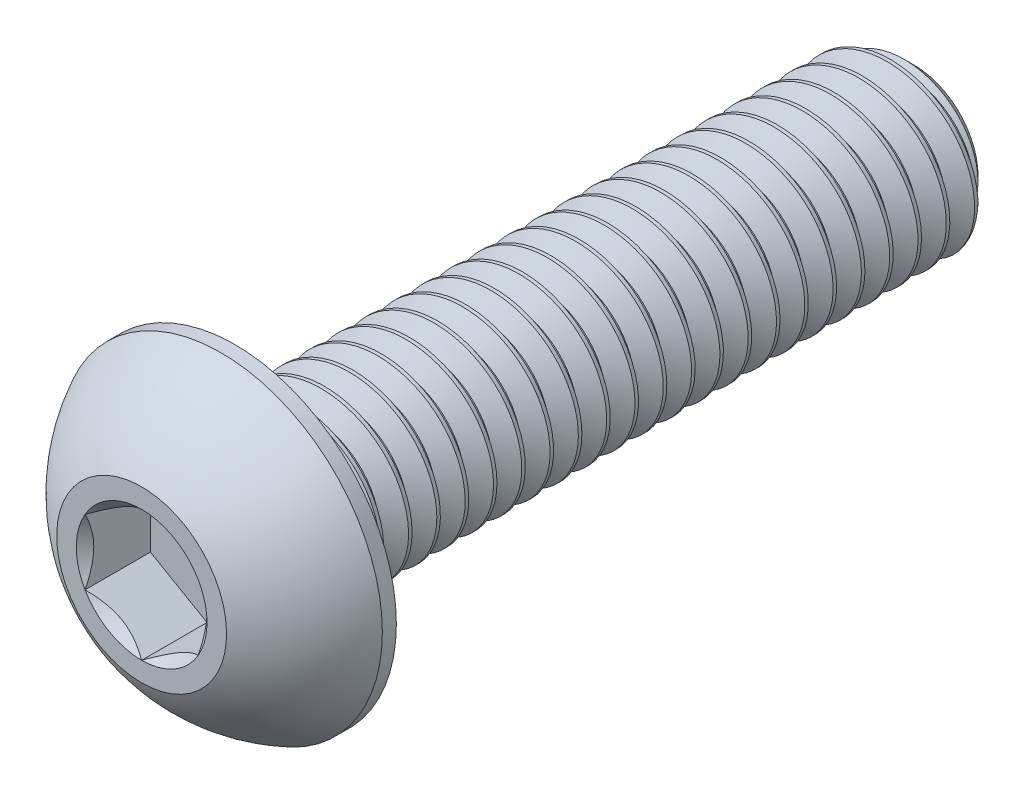
SolidWorks part; units mm, degrees
ref_plane "Front" through (0, 0, 0) normal (0, 0, 1) x (1, 0, 0)
ref_plane "Top" through (0, 0, 0) normal (0, 1, 0) x (1, 0, 0)
ref_plane "Right" through (0, 0, 0) normal (1, 0, 0) x (0, 0, -1)
sketch "Sketch1" plane through (0, 0, 0) normal (1, 0, 0) x (0, 0, -1)
  line L2 (1.65, 1.5) -> (13.65, 1.5)
  line L3 (13.65, 1.5) -> (13.65, 0)
  line L4 (13.65, 0) -> (1.65, 0)
  line L6 (1.4025, 2.85) -> (1.65, 2.85) construction
  line L7 (13.65, 1.5) -> (13.65, -1.5) construction
  line L8 (0, 0) -> (1.65, 0) construction
  line L9 (1.65, 2.85) -> (1.65, -2.85) construction
  line L11 (1.65, 1.5) -> (1.65, 0)
  line L13 (0, 1) -> (0, -1) construction
  line L14 (0, 1) -> (0, 1.5) construction
  arc A3 (0, 1.5) -> (1.4025, 2.85) centre (2.7948, 0) cw construction
  dimension "D1" = 0.2475
revolve "Revolve1" add sketch "Sketch1" angle 360 mid plane about L4
sketch "Sketch3" plane through (0, 0, -13.65) normal (0, 0, -1) x (-1, 0, 0)
  circle A0 centre (0, 0) radius 1.5
curve "Helix/Spiral1" pitch 0.5 height 12.5 radius 1.5 centre (0, 0, -13.65) axis (0, 0, 1) start towards (0, 1, 0)
sketch "Sketch2" plane through (0, 0, 0) normal (1, 0, 0) x (0, 0, -1)
  line L0 (13.65, 1.5) -> (14.0875, 1.5)
  line L1 (14.0875, 1.5) -> (13.9, 1.1752)
  line L2 (13.9, 1.1752) -> (13.8375, 1.1752)
  line L3 (13.8375, 1.1752) -> (13.65, 1.5)
  line L4 (13.7438, 1.3376) -> (13.9938, 1.3376) construction
  dimension "D1" = 60
  dimension "D2" = 0.0625
  dimension "D3" = 0.25
chamfer "Chamfer1" distance 0.375 angle 45 1 edges at (0, 1.5, -13.65)
sweep "Cut-Sweep1" cut profiles "Sketch2" path "Helix/Spiral1" align with end faces yes
sketch "Sketch7" plane through (0, 0, 0) normal (1, 0, 0) x (0, 0, -1)
  line L6 (1.4025, 2.85) -> (1.65, 2.85) construction
  line L8 (0, 0) -> (1.65, 0) construction
  line L11 (1.65, 2.85) -> (1.65, -2.85) construction
  line L12 (1.4025, 2.85) -> (1.65, 2.85)
  line L13 (0, 0) -> (1.65, 0)
  line L14 (0, 1) -> (0, -1) construction
  line L15 (1.65, 2.85) -> (1.65, 0)
  line L16 (0, 1.5) -> (0, 0)
  arc A2 (1.4025, 2.85) -> (0, 1.5) centre (2.7948, 0) ccw construction
  arc A3 (1.4025, 2.85) -> (0, 1.5) centre (2.7948, 0) ccw
revolve "Revolve2" add sketch "Sketch7" angle 360 mid plane about L13
sketch "Sketch5" plane through (0, 0, 0) normal (0, 0, 1) x (1, 0, 0)
  line L1 (1, -0.5774) -> (1, 0.5774)
  line L2 (1, 0.5774) -> (0, 1.1547)
  line L3 (0, 1.1547) -> (-1, 0.5774)
  line L4 (-1, 0.5774) -> (-1, -0.5774)
  line L5 (-1, -0.5774) -> (0, -1.1547)
  line L6 (0, -1.1547) -> (1, -0.5774)
  circle A0 centre (0, 0) radius 1 construction
extrude "Cut-Extrude2" cut sketch "Sketch5" against normal blind 1.155
sketch "Sketch6" plane through (0, 0, 0) normal (0, 0, 1) x (1, 0, 0)
  circle A0 centre (0, 0) radius 1.1547
extrude "Cut-Extrude3" cut sketch "Sketch6" against normal blind 1.155 draft 45
sketch "Sketch9" [suppressed] plane through (0, 0, -4.2164) normal (0, 0, 1) x (1, 0, 0)
  circle A2 centre (0, 0) radius 3.9687
extrude "Boss-Extrude2" [suppressed] add sketch "Sketch9" against normal offset from surface (9.525 mm away) 28.575 up to face at (0, 1.125, -13.65)
sketch "Sketch10" plane through (0, 0, 0) normal (1, 0, 0) x (0, 0, -1)
  line L0 (13.65, 1.5) -> (13.65, -1.5) construction
  point P0 (12.9, -1.5)
  dimension "D1" = 0.75
equation "\"D3@Helix/Spiral1\" = \"Lg@Sketch1\" + \"D4@Helix/Spiral1\""
equation "\"D2@Sketch2\" = \"D4@Helix/Spiral1\" * .125"
equation "\"D3@Sketch2\" = \"D4@Helix/Spiral1\" * .5"
equation "\"D1@Chamfer1\" = \"D4@Helix/Spiral1\" * .75"
equation "\"D1@Cut-Extrude2\" = \"Head Ht@Sketch1\" * .7"
equation "\"D1@Sketch1\" = \"Head Ht@Sketch1\" * .15"
equation "\"D1@Sketch10\" = \"D4@Helix/Spiral1\" * 1.5"
equation "\"D1@Cut-Extrude3\" = \"D1@Cut-Extrude2\""
